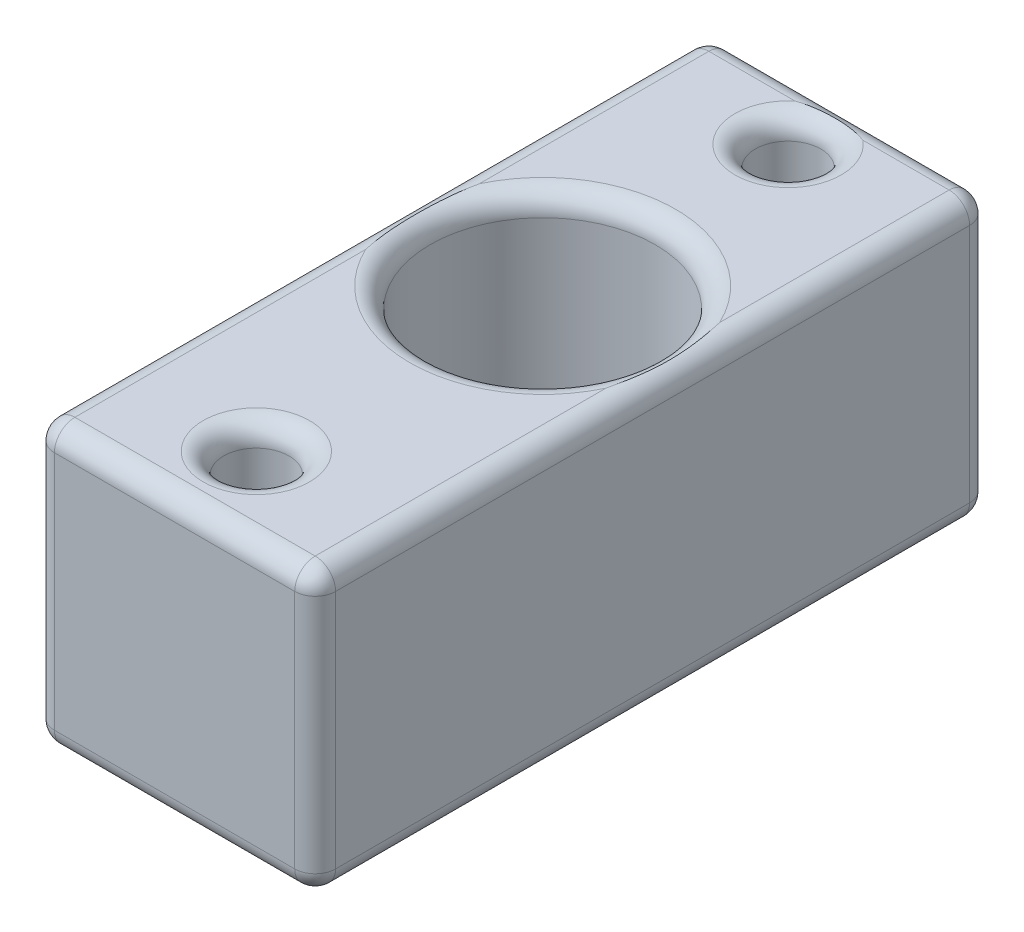
SolidWorks part; units mm, degrees
ref_plane "Front Plane" through (0, 0, 0) normal (0, 0, 1) x (1, 0, 0)
ref_plane "Top Plane" through (0, 0, 0) normal (0, 1, 0) x (1, 0, 0)
ref_plane "Right Plane" through (0, 0, 0) normal (1, 0, 0) x (0, 0, -1)
sketch "Sketch1" plane through (0, 0, 0) normal (0, 0, 1) x (1, 0, 0)
  line L1 (-6.875, -6.875) -> (6.875, -6.875)
  line L2 (-6.875, -6.875) -> (-6.875, 6.875)
  line L3 (-6.875, 6.875) -> (6.875, 6.875)
  line L4 (6.875, -6.875) -> (6.875, 6.875)
  line L5 (-6.875, -6.875) -> (6.875, 6.875) construction
  line L6 (-6.875, 6.875) -> (6.875, -6.875) construction
  point P0 (0, 0)
  dimension "D1" = 13.75
extrude "Boss-Extrude1" add sketch "Sketch1" along normal blind 18 and the other way blind 15
sketch "Sketch2" plane through (0, 0, 0) normal (0, 1, 0) x (1, 0, 0)
  circle A6 centre (0, 12) radius 1.6 construction
  circle A7 centre (0, 12) radius 1.6
  circle A8 centre (0, -14) radius 1.6 construction
  circle A9 centre (0, 0) radius 5.5 construction
  circle A10 centre (0, -14) radius 1.6
  circle A11 centre (0, 0) radius 5.5
extrude "Cut-Extrude1" cut sketch "Sketch2" against normal blind 10 and the other way blind 10
fillet "Fillet1" radius 1 18 edges at (0, 6.875, -15) (-6.875, 0, -15) (0, -6.875, -15) (6.875, 0, -15) (0, -6.875, 18) (-6.875, 0, 18) (0, 6.875, 18) (6.875, 0, 18) (0, -6.875, 12.4) (0, -6.875, -13.6) (0, 6.875, 15.6) (0, 6.875, -10.4) (0, 6.875, 5.5) (0, -6.875, -5.5) (6.875, -6.875, 1.5) (6.875, 6.875, 1.5) (-6.875, 6.875, 1.5) (-6.875, -6.875, 1.5)
